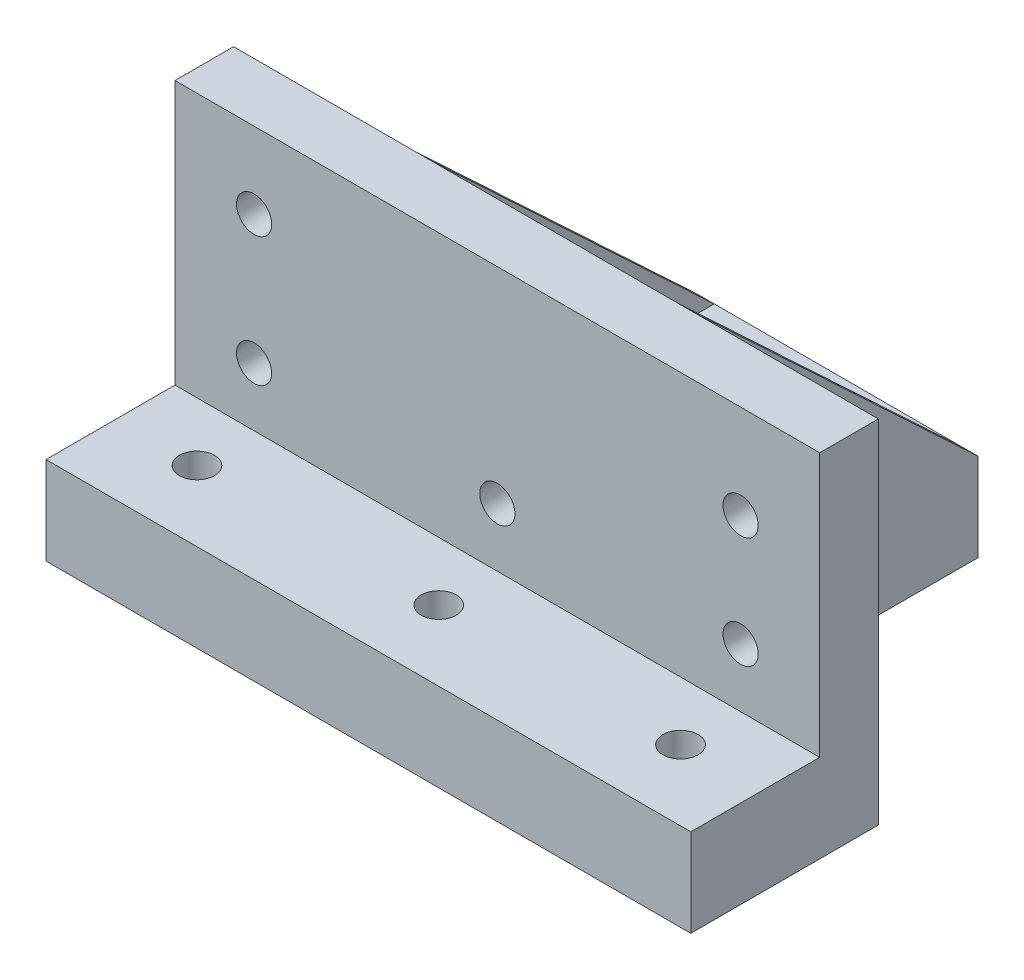
SolidWorks part; units mm, degrees
ref_plane "Спереди" through (0, 0, 0) normal (0, 0, 1) x (1, 0, 0)
ref_plane "Сверху" through (0, 0, 0) normal (0, 1, 0) x (1, 0, 0)
ref_plane "Справа" through (0, 0, 0) normal (1, 0, 0) x (0, 0, -1)
sketch "Эскиз1" plane through (0, 0, 0) normal (0, 1, 0) x (1, 0, 0)
  line L0 (0, 0) -> (-16, 0) construction
  line L1 (0, 0) -> (0, 16) construction
  line L2 (0, -24) -> (0, -56) construction
  line L3 (-24, 24) -> (24, 24)
  line L4 (-24, 24) -> (-24, -24)
  line L6 (24, 24) -> (24, -24)
  line L7 (-24, 24) -> (24, -24) construction
  line L8 (-24, -24) -> (24, 24) construction
  line L9 (0, -56) -> (-55, -56) construction
  line L10 (0, -56) -> (55, -56) construction
  line L11 (24, -24) -> (55, -24)
  line L12 (-55, -56) -> (55, -56)
  line L13 (-55, -56) -> (-55, -24)
  line L14 (-55, -24) -> (-24, -24)
  line L15 (55, -56) -> (55, -24)
  circle A0 centre (0, 0) radius 12
  circle A1 centre (-16, 16) radius 1.75
  circle A2 centre (16, 16) radius 1.75
  circle A3 centre (16, -16) radius 1.75
  circle A4 centre (-16, -16) radius 1.75
  dimension "D1" = 24
  dimension "D4" = 3.5
  dimension "D2" = 16
  dimension "D3" = 16
  dimension "D7" = 48
  dimension "D8" = 32
  dimension "D9" = 55
  dimension "D10" = 55
  dimension "D5" = 2
  dimension "D6" = 2
extrude "Бобышка-Вытянуть1" add sketch "Эскиз1" along normal blind 15
sketch "Эскиз2" plane through (0, 15, 0) normal (0, 1, 0) x (1, 0, 0)
  line L0 (55, -56) -> (55, -24) construction
  line L1 (-55, -24) -> (55, -24)
  line L2 (-55, -24) -> (-55, -34)
  line L3 (-55, -34) -> (55, -34)
  line L4 (55, -24) -> (55, -34)
  dimension "D1" = 10
extrude "Бобышка-Вытянуть2" add sketch "Эскиз2" along normal blind 45
sketch "Эскиз5" plane through (0, 15, 0) normal (0, 1, 0) x (1, 0, 0)
  line L0 (-55, -66.2734) -> (55, -66.2734) construction
  line L1 (-55, -71.1392) -> (0, -71.1392) construction
  line L2 (-55, -80.1997) -> (-27.5, -80.1997) construction
  line L3 (55, -80.1997) -> (27.5, -80.1997) construction
  line L4 (-58.0091, -56) -> (-58.0091, -34) construction
  line L5 (-60.3127, -34) -> (-60.3127, -54) construction
  circle A0 centre (-41.25, -44) radius 3
  circle A1 centre (0, -44) radius 3
  circle A2 centre (41.25, -44) radius 3
  dimension "D1" = 6
  dimension "D2" = 6
  dimension "D4" = 6
  dimension "D3" = 27.5
  dimension "D5" = 20
extrude "Вырез-Вытянуть2" cut sketch "Эскиз5" against normal through all
sketch "Эскиз6" plane through (0, 0, 0) normal (0, -1, 0) x (1, 0, 0)
  circle A0 centre (-41.25, 44) radius 5
  circle A1 centre (0, 44) radius 5
  circle A2 centre (41.25, 44) radius 5
  dimension "D1" = 10
  dimension "D2" = 10
  dimension "D3" = 10
extrude "Вырез-Вытянуть3" cut sketch "Эскиз6" against normal blind 10
sketch "Эскиз7" plane through (0, 0, 34) normal (0, 0, 1) x (1, 0, 0)
  line L0 (-59.6742, 15) -> (-59.6742, 38) construction
  line L1 (-69.9041, 15) -> (-69.9041, 35) construction
  line L2 (-55, 47.894) -> (-28, 47.894) construction
  line L3 (55, 47.894) -> (28, 47.894) construction
  circle A0 centre (-41.5, 25) radius 3
  circle A1 centre (41.5, 25) radius 3
  circle A2 centre (0, 25) radius 3
  dimension "D4" = 6
  dimension "D5" = 6
  dimension "D6" = 6
  dimension "D1" = 20
  dimension "D2" = 27
  dimension "D3" = 27
extrude "Вырез-Вытянуть4" cut sketch "Эскиз7" against normal through all
sketch "Эскиз8" plane through (0, 0, 24) normal (0, 0, -1) x (-1, 0, 0)
  circle A0 centre (-41.5, 25) radius 5
  circle A1 centre (0, 25) radius 5
  circle A2 centre (41.5, 25) radius 5
  dimension "D1" = 10
  dimension "D2" = 10
  dimension "D3" = 10
extrude "Вырез-Вытянуть5" cut sketch "Эскиз8" against normal blind 5
sketch "Эскиз10" plane through (24, 0, 0) normal (1, 0, 0) x (0, 0, -1)
  line L0 (-24, 15) -> (-24, 60)
  line L1 (-24, 60) -> (24, 15)
  line L2 (24, 15) -> (-24, 15)
extrude "Бобышка-Вытянуть3" add sketch "Эскиз10" against normal blind 3
sketch "Эскиз11" plane through (-24, 0, 0) normal (-1, 0, 0) x (0, 0, 1)
  line L0 (24, 15) -> (-24, 15)
  line L1 (-24, 15) -> (24, 60)
  line L2 (24, 60) -> (24, 15)
extrude "Бобышка-Вытянуть4" add sketch "Эскиз11" against normal blind 3
sketch "Эскиз14" plane through (0, 0, 34) normal (0, 0, 1) x (1, 0, 0)
  circle A0 centre (-41.5, 47.0048) radius 3
  circle A1 centre (41.5, 44.0048) radius 3
  dimension "D1" = 6
  dimension "D2" = 6
extrude "Вырез-Вытянуть9" cut sketch "Эскиз14" against normal through all
sketch "Эскиз15" plane through (0, 0, 24) normal (0, 0, -1) x (-1, 0, 0)
  circle A0 centre (41.5, 47.0048) radius 5
  circle A1 centre (-41.5, 44.0048) radius 5
  dimension "D1" = 10
  dimension "D2" = 10
extrude "Вырез-Вытянуть10" cut sketch "Эскиз15" against normal blind 5
